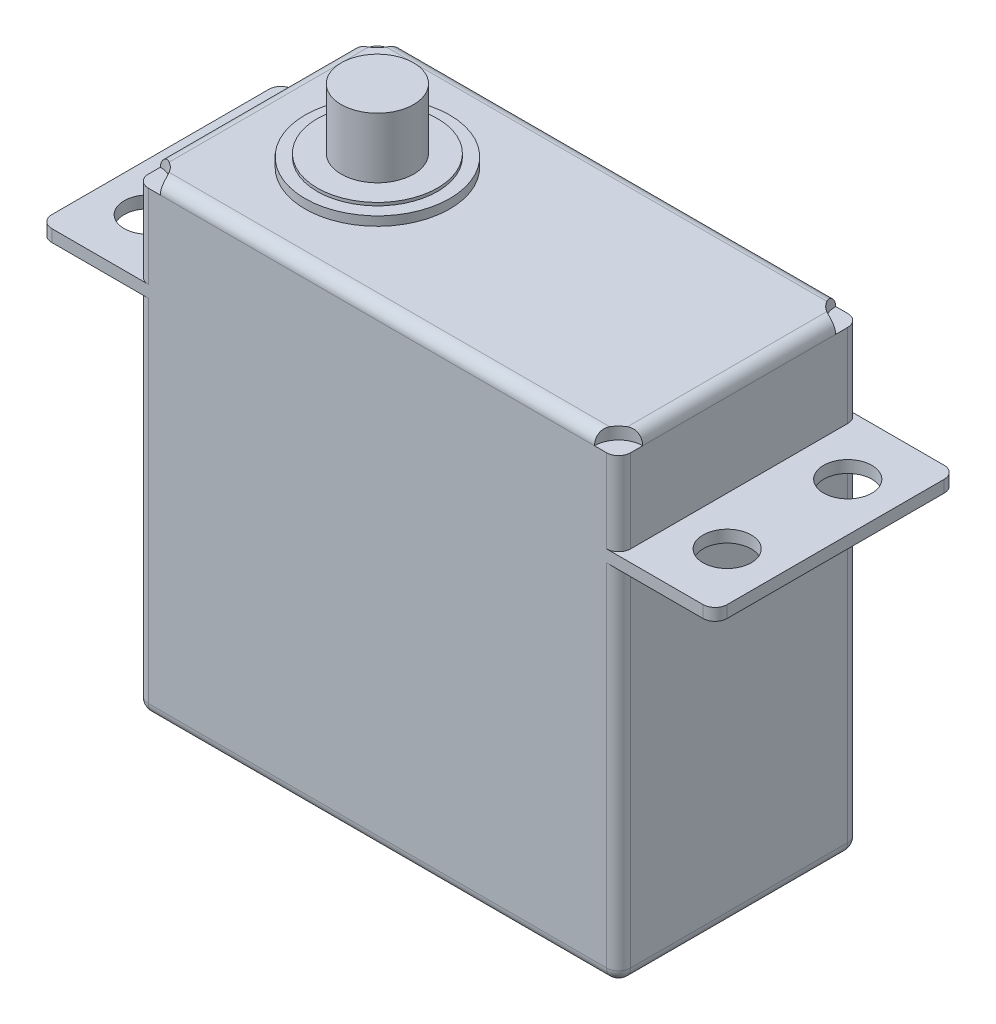
SolidWorks part; units mm, degrees
ref_plane "前视基准面" through (0, 0, 0) normal (0, 0, 1) x (1, 0, 0)
ref_plane "上视基准面" through (0, 0, 0) normal (0, 1, 0) x (1, 0, 0)
ref_plane "右视基准面" through (0, 0, 0) normal (1, 0, 0) x (0, 0, -1)
other "Configuration Table"
sketch "草图1" plane through (0, 0, 0) normal (0, 1, 0) x (1, 0, 0)
  line L1 (-20, -5) -> (20, -5)
  line L2 (-20, -5) -> (-20, 5)
  line L3 (-20, 5) -> (20, 5)
  line L4 (20, -5) -> (20, 5)
  line L5 (-20, -5) -> (20, 5) construction
  line L6 (-20, 5) -> (20, -5) construction
  point P0 (0, 0)
  point P6 (-35.2926, 11.6262)
extrude "凸台-拉伸2" add sketch "草图1" along normal blind 39
sketch "草图2" plane through (-20, 0, 0) normal (-1, 0, 0) x (0, 0, 1)
  line L0 (0, 0) -> (0, 31)
sketch "草图4" plane through (-20, 0, 0) normal (-1, 0, 0) x (0, 0, 1)
  line L0 (-5, 39) -> (-5, 0) construction
  line L1 (-5, 31.0964) -> (5, 31.0964)
  line L2 (-5, 31.0964) -> (-5, 30.0964)
  line L3 (-5, 30.0964) -> (5, 30.0964)
  line L4 (5, 31.0964) -> (5, 30.0964)
  line L5 (5, 39) -> (5, 0) construction
  dimension "D1" = 1
extrude "凸台-拉伸8" add sketch "草图4" along normal blind 8 contours L2 L3 L4 L1
sketch "草图12" plane through (20, 0, 0) normal (1, 0, 0) x (0, 0, -1)
  line L1 (-5, 31.0964) -> (5, 31.0964)
  line L2 (-5, 31.0964) -> (-5, 30.0964)
  line L3 (-5, 30.0964) -> (5, 30.0964)
  line L4 (5, 31.0964) -> (5, 30.0964)
extrude "凸台-拉伸9" add sketch "草图12" along normal blind 8
sketch "草图14" plane through (0, 0, 0) normal (0, -1, 0) x (1, 0, 0)
  line L3 (20, -10) -> (-20, -10)
  line L4 (20, -10) -> (20, 10)
  line L5 (20, 10) -> (-20, 10)
  line L6 (-20, -10) -> (-20, 10)
  line L7 (20, -10) -> (-20, 10) construction
  line L8 (20, 10) -> (-20, -10) construction
  point P4 (0, 0)
  dimension "D1" = 20
  dimension "D2" = 40
extrude "凸台-拉伸10" add sketch "草图14" against normal blind 39
sketch "草图15" plane through (-20, 0, 0) normal (-1, 0, 0) x (0, 0, 1)
  line L0 (-10, 39) -> (-10, 0) construction
  line L1 (-10, 31.0964) -> (10, 31.0964)
  line L2 (-10, 31.0964) -> (-10, 30.0964)
  line L3 (-10, 30.0964) -> (10, 30.0964)
  line L4 (10, 31.0964) -> (10, 30.0964)
  line L5 (10, 39) -> (10, 0) construction
extrude "凸台-拉伸12" add sketch "草图15" along normal blind 8
sketch "草图16" plane through (20, 0, 0) normal (1, 0, 0) x (0, 0, -1)
  line L1 (-10, 31.0964) -> (10, 31.0964)
  line L2 (-10, 31.0964) -> (-10, 30.0964)
  line L3 (-10, 30.0964) -> (10, 30.0964)
  line L4 (10, 31.0964) -> (10, 30.0964)
extrude "凸台-拉伸13" add sketch "草图16" along normal blind 8
sketch "草图17" plane through (0, 39, 0) normal (0, 1, 0) x (1, 0, 0)
  line L0 (-20, 0) -> (-10, 0) construction
  line L1 (-20, 10) -> (-20, -10) construction
  circle A0 centre (-10, 0) radius 6
  point P6 (0, 0)
extrude "凸台-拉伸15" add sketch "草图17" along normal blind 0.75 contours A0
sketch "草图19" plane through (0, 39.75, 0) normal (0, 1, 0) x (1, 0, 0)
  circle A0 centre (-10, 0) radius 4.986
extrude "凸台-拉伸16" add sketch "草图19" along normal blind 0.25
sketch "草图20" plane through (0, 40, 0) normal (0, 1, 0) x (1, 0, 0)
  circle A0 centre (-10, 0) radius 3
extrude "凸台-拉伸17" add sketch "草图20" along normal blind 5
sketch "草图21" plane through (0, 31.0964, 0) normal (0, 1, 0) x (1, 0, 0)
  line L0 (-24, 10) -> (-24, 5) construction
  line L1 (-28, 10) -> (-20, 10) construction
  line L2 (-24, -10) -> (-24, -5)
  line L3 (-28, -10) -> (-20, -10) construction
sketch "草图22" plane through (0, 31.0964, 0) normal (0, 1, 0) x (1, 0, 0)
  circle A0 centre (-24, 5) radius 2
  circle A1 centre (-24, -5) radius 2
extrude "切除-拉伸1" cut sketch "草图22" against normal blind 5
sketch "草图23" plane through (0, 31.0964, 0) normal (0, 1, 0) x (1, 0, 0)
  circle A0 centre (24, 5) radius 2
  circle A1 centre (24, -5) radius 2
extrude "切除-拉伸3" cut sketch "草图23" against normal blind 5
fillet "圆角12" radius 1 4 edges at (-20, 0, 0) (0, 0, 10) (20, 0, 0) (0, 0, -10)
fillet "圆角13" radius 1 8 edges at (19.7071, 0.2929, -9.7071) (19.7071, 0.2929, 9.7071) (-19.7071, 0.2929, 9.7071) (-19.7071, 0.2929, -9.7071) (20, 15.5482, -10) (20, 15.5482, 10) (-20, 15.5482, 10) (-20, 15.5482, -10)
sketch "草图27" plane through (0, 39, 0) normal (0, 1, 0) x (1, 0, 0)
  circle A0 centre (-20, 10) radius 2
  circle A1 centre (20, 10) radius 2
  circle A2 centre (20, -10) radius 2
  circle A3 centre (-20, -10) radius 2
extrude "切除-拉伸4" cut sketch "草图27" against normal blind 1
fillet "圆角14" radius 1 4 edges at (20, 34.5482, -10) (20, 34.5482, 10) (-20, 34.5482, 10) (-20, 34.5482, -10)
fillet "圆角15" radius 1 4 edges at (-20, 39, 0) (20, 39, 0) (0, 39, -10) (0, 39, 10)
fillet "圆角16" radius 1 4 edges at (28, 30.5964, 10) (28, 30.5964, -10) (-28, 30.5964, -10) (-28, 30.5964, 10)
equation "\"·\"=5"
